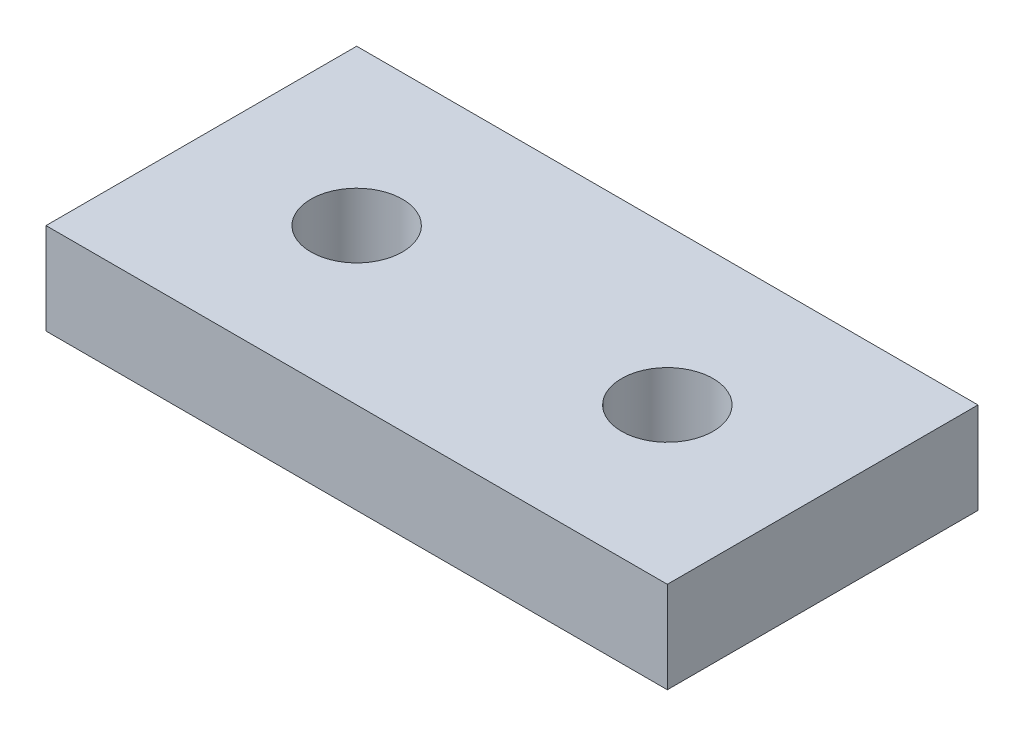
SolidWorks part; units mm, degrees
ref_plane "Front Plane" through (0, 0, 0) normal (0, 0, 1) x (1, 0, 0)
ref_plane "Top Plane" through (0, 0, 0) normal (0, 1, 0) x (1, 0, 0)
ref_plane "Right Plane" through (0, 0, 0) normal (1, 0, 0) x (0, 0, -1)
other "Configuration Table"
sketch "sketch1" plane through (0, 0, 0) normal (0, 1, 0) x (1, 0, 0)
  line L0 (0, -8.5) -> (8.5, -8.5) construction
  line L1 (0, 0) -> (34, 0)
  line L2 (0, 0) -> (0, -17)
  line L3 (0, -17) -> (34, -17)
  line L4 (34, 0) -> (34, -17)
  line L5 (8.5, -8.5) -> (25.5, -8.5) construction
  circle A1 centre (8.5, -8.5) radius 2.505
  circle A2 centre (25.5, -8.5) radius 2.505
  dimension "D4" = 5.01
  dimension "D1" = 17
  dimension "D2" = 34
  dimension "D3" = 8.5
  dimension "D6" = 17
  dimension "D5" = 2
extrude "Boss-Extrude1" add sketch "sketch1" along normal blind 5
equation "\"D2@sketch1\" = \"length\""
equation "\"holes\"= 2"
equation "\"cdist\"= 17mm'centre distance between holes"
equation "\"width\"= 17mm"
equation "\"length\"= \"cdist\" * \"holes\""
equation "\"D1@sketch1\" = \"width\""
equation "\"hdiam\"= 5.01mm'Hole diametre"
equation "\"D4@sketch1\" = \"hdiam\""
equation "\"D6@sketch1\" = \"cdist\""
equation "\"D5@sketch1\" = \"holes\""
equation "\"D1@Boss-Extrude1\"=\"height\""
equation "\"height\"= 5mm'Height of extrude"
